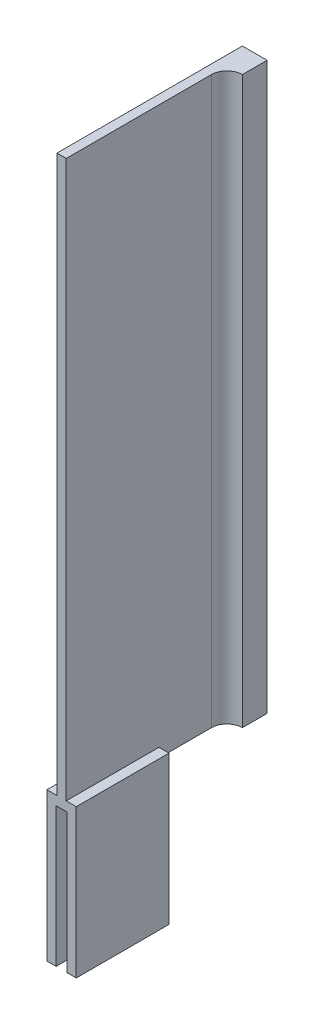
SolidWorks part; units mm, degrees
ref_plane "前视基准面" through (0, 0, 0) normal (0, 0, 1) x (1, 0, 0)
ref_plane "上视基准面" through (0, 0, 0) normal (0, 1, 0) x (1, 0, 0)
ref_plane "右视基准面" through (0, 0, 0) normal (1, 0, 0) x (0, 0, -1)
sketch "草图1" plane through (0, 0, 0) normal (0, 0, 1) x (1, 0, 0)
  line L1 (0, 0) -> (3, 0)
  line L2 (0, 0) -> (0, 45)
  line L3 (0, 45) -> (3, 45)
  line L4 (3, 0) -> (3, 45)
  line L5 (6.5, 0) -> (9.5, 0)
  line L6 (6.5, 0) -> (6.5, 45)
  line L7 (6.5, 45) -> (9.5, 45)
  line L8 (9.5, 0) -> (9.5, 45)
  dimension "D1" = 3
  dimension "D2" = 45
  dimension "D3" = 3
  dimension "D4" = 3.5
  dimension "D5" = 45
extrude "凸台-拉伸1" add sketch "草图1" along normal blind 30
sketch "草图2" plane through (0, 45, 0) normal (0, 1, 0) x (1, 0, 0)
  line L1 (0, 0) -> (9.5, 0)
  line L2 (0, 0) -> (0, -30)
  line L3 (0, -30) -> (9.5, -30)
  line L4 (9.5, 0) -> (9.5, -30)
extrude "凸台-拉伸2" add sketch "草图2" along normal blind 3
sketch "草图3" plane through (0, 48, 0) normal (0, 1, 0) x (1, 0, 0)
  line L0 (4.75, 0) -> (4.75, -30) construction
  line L1 (3.25, 30) -> (6.25, 30)
  line L2 (3.25, 30) -> (3.25, -30)
  line L3 (3.25, -30) -> (6.25, -30)
  line L4 (6.25, 30) -> (6.25, -30)
  line L5 (9.5, 0) -> (0, 0) construction
  line L6 (0, -30) -> (9.5, -30) construction
  line L8 (4.75, 30) -> (4.75, -30) construction
  dimension "D1" = 60
  dimension "D2" = 3
extrude "凸台-拉伸3" add sketch "草图3" along normal blind 180 contours L2 L3 L4 L1
sketch "草图4" plane through (0, 228, 0) normal (0, 1, 0) x (1, 0, 0)
  line L1 (-1.75, 22) -> (3.25, 22)
  line L2 (-1.75, 22) -> (-1.75, 30)
  line L3 (-1.75, 30) -> (3.25, 30)
  line L4 (3.25, 22) -> (3.25, 30)
  dimension "D1" = 5
  dimension "D2" = 8
extrude "凸台-拉伸4" add sketch "草图4" against normal up to surface (180 mm away) up to face at (7.875, 48, 15)
fillet "圆角4" radius 5 1 edges at (3.25, 138, -22)
ref_plane "基准面1" through (16.25, 0, 0) normal (1, 0, 0) x (0, 0, -1)
mirror "镜向3" about plane through (16.25, 0, 0) normal (1, 0, 0) of bodies 107
sketch "草图5" plane through (16.25, 0, 0) normal (1, 0, 0) x (0, 0, -1)
  line L1 (-30, 228) -> (30.0887, 228)
  line L2 (-30, 228) -> (-30, 0)
  line L3 (-30, 0) -> (30.0887, 0)
  line L4 (30.0887, 228) -> (30.0887, 0)
extrude "切除-拉伸1" cut sketch "草图5" against normal up to next
sketch "草图6" plane through (0, 48, 0) normal (0, -1, 0) x (1, 0, 0)
  line L5 (26.25, 0) -> (26.25, -30)
  line L6 (26.25, -30) -> (34.25, -30)
  line L7 (34.25, -30) -> (34.25, -22)
  line L8 (29.25, -17) -> (29.25, 0)
  line L9 (29.25, 0) -> (26.25, 0)
  line L10 (26.25, 0) -> (26.25, -30)
  line L11 (26.25, -30) -> (34.25, -30)
  line L12 (34.25, -30) -> (34.25, -22)
  line L13 (29.25, -17) -> (29.25, 0)
  line L14 (29.25, 0) -> (26.25, 0)
  arc A1 (29.25, -17) -> (34.25, -22) centre (34.25, -17) ccw
  arc A2 (29.25, -17) -> (34.25, -22) centre (34.25, -17) ccw
  dimension "D1" = 0
extrude "凸台-拉伸5" add sketch "草图6" along normal up to surface (3 mm away) up to face at (27.75, 45, 15)
